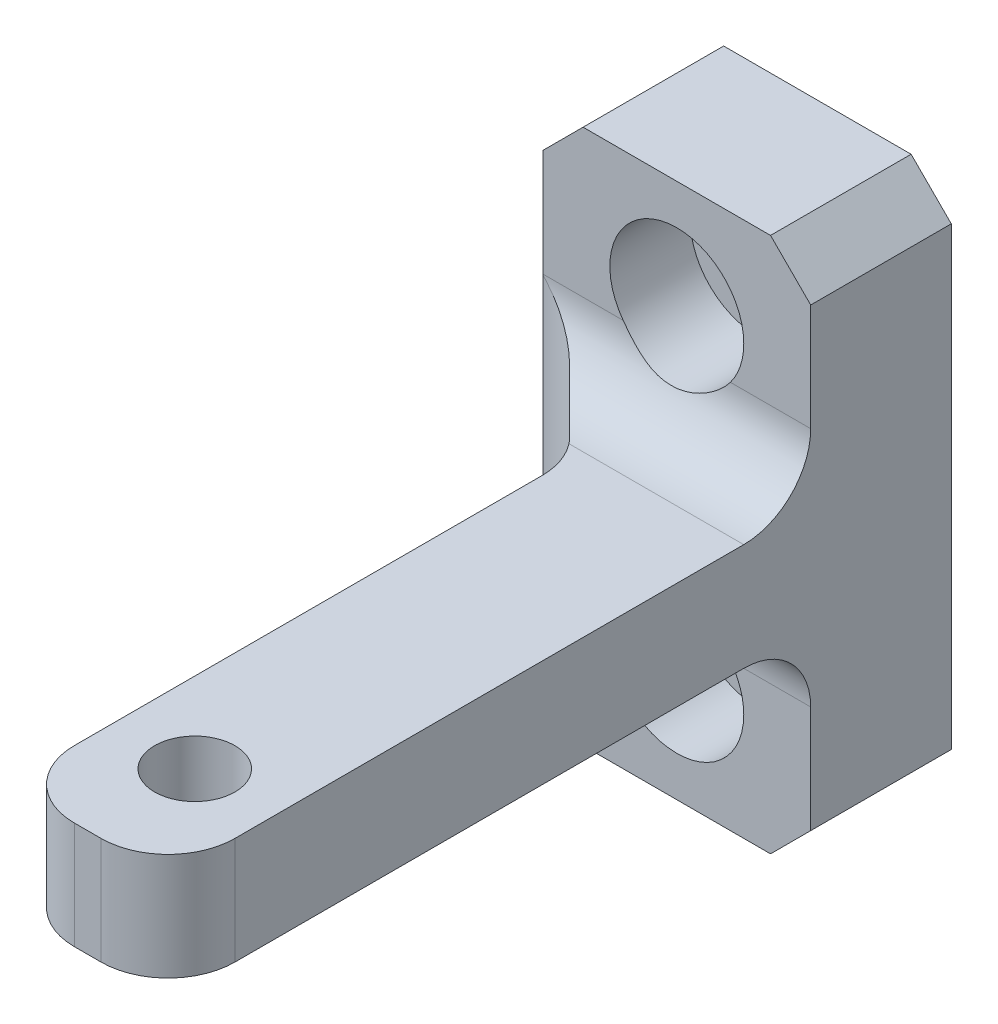
SolidWorks part; units mm, degrees
ref_plane "Front Plane" through (0, 0, 0) normal (0, 0, 1) x (1, 0, 0)
ref_plane "Top Plane" through (0, 0, 0) normal (0, 1, 0) x (1, 0, 0)
ref_plane "Right Plane" through (0, 0, 0) normal (1, 0, 0) x (0, 0, -1)
sketch "Sketch1" plane through (0, 0, 0) normal (0, 1, 0) x (1, 0, 0)
  line L0 (0, 0) -> (0, 44) construction
  line L2 (10, -7.25) -> (-2, -7.25)
  line L3 (10, -7.25) -> (10, 51.25)
  line L4 (10, 51.25) -> (-10, 51.25)
  line L5 (-10, 40.75) -> (-10, 51.25)
  line L6 (10, -7.25) -> (-10, 51.25) construction
  line L7 (10, 51.25) -> (-2, 16.15) construction
  line L10 (-10, 40.75) -> (-2, 40.75)
  line L11 (-2, -7.25) -> (-2, 40.75)
  point P3 (0, 22)
  dimension "D1" = 58.5
  dimension "D2" = 20
  dimension "D3" = 48
  dimension "D4" = 8
extrude "Boss-Extrude1" add sketch "Sketch1" along normal blind 8
sketch "Sketch2" plane through (0, 0, -51.25) normal (0, 0, -1) x (-1, 0, 0)
  line L0 (-10, 4) -> (10, 4) construction
  line L1 (-10, 8) -> (-10, 0) construction
  line L2 (10, 8) -> (10, 0) construction
  line L3 (0, 8) -> (0, 24) construction
  line L4 (-10, -16) -> (10, -16)
  line L5 (-10, -16) -> (-10, 24)
  line L6 (-10, 24) -> (10, 24)
  line L7 (10, -16) -> (10, 24)
  line L8 (-10, -16) -> (10, 24) construction
  line L9 (-10, 24) -> (10, -16) construction
  line L10 (-10, 8) -> (10, 8) construction
  circle A0 centre (0, 16) radius 2.65
  circle A1 centre (0, -8) radius 2.65
  point P6 (0, 4)
  dimension "D1" = 40
  dimension "D2" = 20
extrude "Boss-Extrude2" add sketch "Sketch2" against normal up to surface (10.5 mm away) up to face at (-6, 4, -40.75)
chamfer "Chamfer1" distance 3 angle 45 4 edges at (-10, 24, -46) (10, 24, -46) (10, -16, -46) (-10, -16, -46)
sketch "Sketch3" plane through (0, 0, -40.75) normal (0, 0, 1) x (1, 0, 0)
  circle A0 centre (0, 16) radius 5
  circle A1 centre (0, -8) radius 5
extrude "Cut-Extrude1" cut sketch "Sketch3" against normal blind 6
chamfer "Chamfer2" distance 6 angle 45 1 edges at (-2, 4, -40.75)
sketch "Sketch4" plane through (0, 8, 0) normal (0, 1, 0) x (1, 0, 0)
  line L0 (4, -7.25) -> (4, 0.75) construction
  line L1 (-2, -7.25) -> (10, -7.25) construction
  circle A0 centre (4, 0.75) radius 3
  dimension "D1" = 8
  dimension "D2" = 6
extrude "Cut-Extrude2" cut sketch "Sketch4" against normal up to surface (8 mm away) up to face at (1.6, 0, -20.35)
fillet "Fillet1" radius 5 2 edges at (10, 4, 7.25) (-2, 4, 7.25)
fillet "Fillet2" radius 5 1 edges at (-2, 4, -34.75)
fillet "Fillet3" radius 5 3 edges at (1, 8, -40.75) (-8, 4, -40.75) (1, 0, -40.75)
